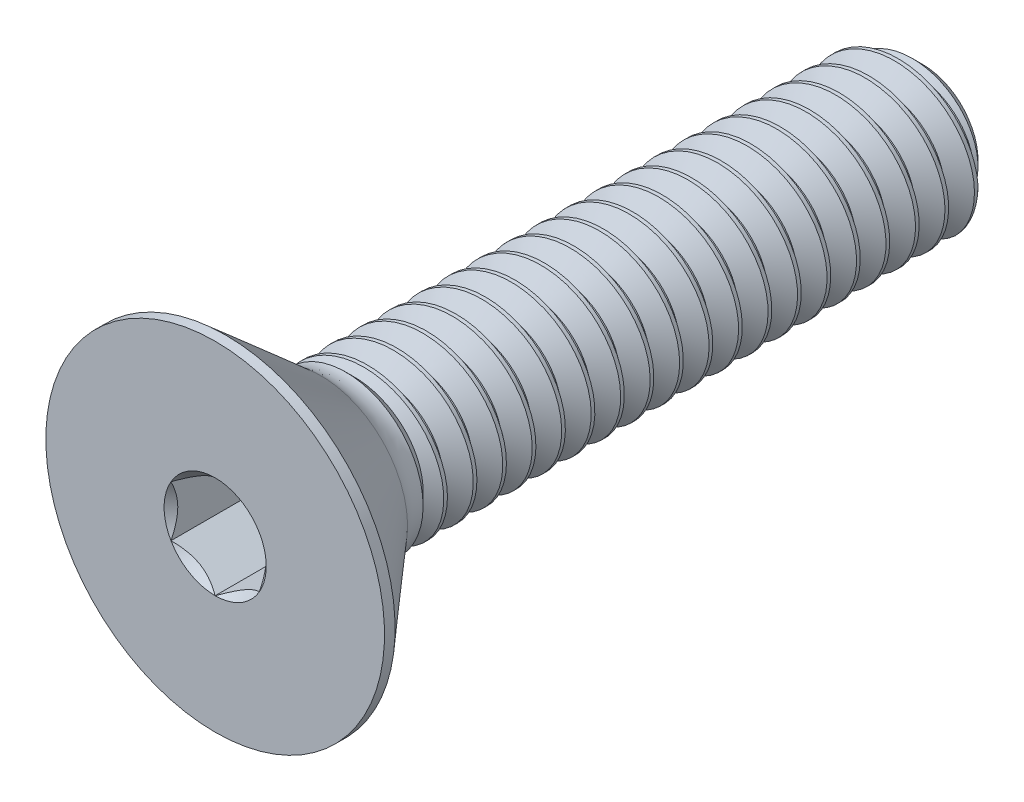
SolidWorks part; units mm, degrees
ref_plane "Front" through (0, 0, 0) normal (0, 0, 1) x (1, 0, 0)
ref_plane "Top" through (0, 0, 0) normal (0, 1, 0) x (1, 0, 0)
ref_plane "Right" through (0, 0, 0) normal (1, 0, 0) x (0, 0, -1)
sketch "Sketch1" plane through (0, 0, 0) normal (1, 0, 0) x (0, 0, -1)
  line L0 (0, 4.5593) -> (0.2845, 4.5593) construction
  line L1 (0.2845, 4.5593) -> (2.8448, 2.3336) construction
  line L2 (0, 2.0828) -> (19.05, 2.0828)
  line L3 (19.05, 2.0828) -> (19.05, 0)
  line L4 (19.05, 0) -> (0, 0)
  line L5 (0, 0) -> (0, 4.5593) construction
  line L6 (0, 4.5593) -> (0, -4.5593) construction
  line L7 (19.05, 2.0828) -> (19.05, -2.0828) construction
  line L8 (0, -4.5593) -> (0.2845, -4.5593) construction
  line L9 (0.2845, -4.5593) -> (2.8448, -2.3336) construction
  line L11 (0, 2.0828) -> (0, 0)
  line L12 (3.5157, 2.0828) -> (3.5157, 0) construction
  arc A1 (2.8448, 2.3336) -> (3.5157, 2.0828) centre (3.5157, 3.1055) ccw construction
  dimension "D1" = 0.2845
revolve "Revolve1" add sketch "Sketch1" angle 360 mid plane about L4
sketch "Sketch3" plane through (0, 0, -19.05) normal (0, 0, -1) x (-1, 0, 0)
  circle A0 centre (0, 0) radius 2.0828
curve "Helix/Spiral1" pitch 0.7937 height 19.05 turns 24
sketch "Sketch2" plane through (0, 0, 0) normal (1, 0, 0) x (0, 0, -1)
  line L0 (19.05, 2.0828) -> (19.7445, 2.0828)
  line L1 (19.7445, 2.0828) -> (19.4469, 1.5672)
  line L2 (19.4469, 1.5672) -> (19.3477, 1.5672)
  line L3 (19.3477, 1.5672) -> (19.05, 2.0828)
  line L4 (19.1988, 1.825) -> (19.5957, 1.825) construction
  dimension "D1" = 60
  dimension "D2" = 0.0992
  dimension "D3" = 0.3969
chamfer "Chamfer1" distance 0.5953 angle 45 1 edges at (0, 2.0828, -19.05)
sweep "Cut-Sweep1" cut profiles "Sketch2" path "Helix/Spiral1"
sketch "Sketch7" plane through (0, 0, 0) normal (1, 0, 0) x (0, 0, -1)
  line L0 (0, 4.5593) -> (0.2845, 4.5593) construction
  line L1 (0.2845, 4.5593) -> (2.8448, 2.3336) construction
  line L2 (0, 4.5593) -> (0.2845, 4.5593)
  line L3 (0.2845, 4.5593) -> (2.8448, 2.3336)
  line L4 (3.5157, 2.0828) -> (3.5157, 0) construction
  line L5 (3.5157, 2.0828) -> (3.5157, 0)
  line L7 (0, 0) -> (0, 4.5593) construction
  line L8 (0, 0) -> (0, 4.5593)
  line L9 (0, 0) -> (3.5157, 0)
  line L10 (5.0152, 0) -> (-5.0152, 0) construction
  arc A0 (2.8448, 2.3336) -> (3.5157, 2.0828) centre (3.5157, 3.1055) ccw construction
  arc A1 (2.8448, 2.3336) -> (3.5157, 2.0828) centre (3.5157, 3.1055) ccw
revolve "Revolve2" add sketch "Sketch7" angle 360 mid plane about L9
ref_plane "Plane1" through (0, 0, -3.5157) normal (0, 0, 1) x (1, 0, 0)
sketch "Sketch8" plane through (0, 0, -3.5157) normal (0, 0, 1) x (1, 0, 0)
  circle A0 centre (0, 0) radius 2.0828
extrude "Boss-Extrude1" add sketch "Sketch8" against normal through all draft 45
sketch "Sketch5" plane through (0, 0, 0) normal (0, 0, 1) x (1, 0, 0)
  line L1 (1.1906, -0.6874) -> (1.1906, 0.6874)
  line L2 (1.1906, 0.6874) -> (0, 1.3748)
  line L3 (0, 1.3748) -> (-1.1906, 0.6874)
  line L4 (-1.1906, 0.6874) -> (-1.1906, -0.6874)
  line L5 (-1.1906, -0.6874) -> (0, -1.3748)
  line L6 (0, -1.3748) -> (1.1906, -0.6874)
  circle A0 centre (0, 0) radius 1.1906 construction
  dimension "Hex" = 2.3813
extrude "Cut-Extrude2" cut sketch "Sketch5" against normal blind 1.9914
sketch "Sketch6" plane through (0, 0, 0) normal (0, 0, 1) x (1, 0, 0)
  circle A0 centre (0, 0) radius 1.3748
extrude "Cut-Extrude3" cut sketch "Sketch6" against normal blind 1.9914 draft 45
sketch "Sketch9" [suppressed] plane through (0, 0, -3.5157) normal (0, 0, 1) x (1, 0, 0)
  circle A1 centre (0, 0) radius 2.0828
  circle A2 centre (0, 0) radius 2.0828
  point P0 (0, 2.0828)
  dimension "D1" = 0
extrude "Boss-Extrude2" [suppressed] add sketch "Sketch9" against normal offset from surface (6.0093 mm away) 22.225
sketch "Sketch10" plane through (0, 0, 0) normal (1, 0, 0) x (0, 0, -1)
  line L0 (19.05, 2.0828) -> (19.05, -2.0828) construction
  point P0 (17.8594, -2.0828)
  dimension "D1" = 1.1906
equation "\"D3@Helix/Spiral1\" = \"Lg@Sketch1\""
equation "\"D2@Sketch2\" = \"D4@Helix/Spiral1\" * .125"
equation "\"D3@Sketch2\" = \"D4@Helix/Spiral1\" * .5"
equation "\"D1@Chamfer1\" = \"D4@Helix/Spiral1\" * .75"
equation "\"D1@Cut-Extrude2\" = \"Head Ht@Sketch1\" * .7"
equation "\"D1@Sketch1\" = \"Head Ht@Sketch1\" * .1"
equation "\"D1@Sketch10\" = \"D4@Helix/Spiral1\" * 1.5"
equation "\"D1@Cut-Extrude3\" = \"D1@Cut-Extrude2\""
